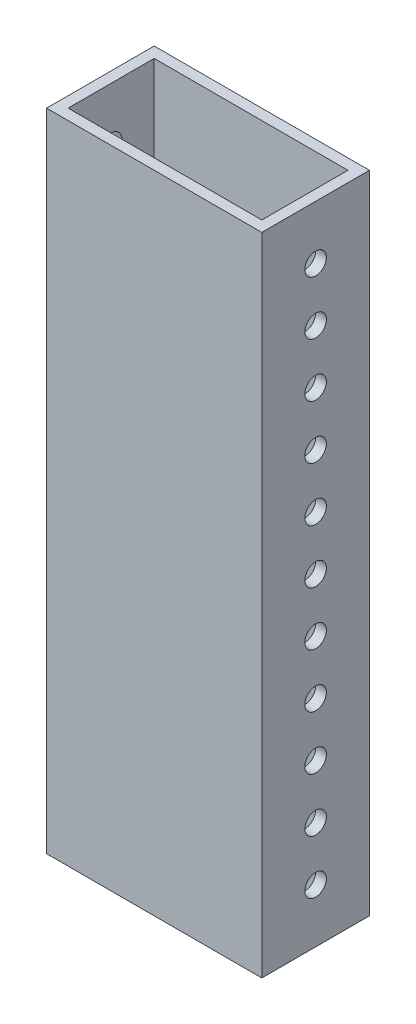
SolidWorks part; units mm, degrees
ref_plane "Front Plane" through (0, 0, 0) normal (0, 0, 1) x (1, 0, 0)
ref_plane "Top Plane" through (0, 0, 0) normal (0, 1, 0) x (1, 0, 0)
ref_plane "Right Plane" through (0, 0, 0) normal (1, 0, 0) x (0, 0, -1)
sketch "Sketch1" plane through (0, 0, 0) normal (0, 1, 0) x (1, 0, 0)
  line L1 (-59.9507, 17.7211) -> (-9.1507, 17.7211)
  line L2 (-59.9507, 17.7211) -> (-59.9507, -7.6789)
  line L3 (-59.9507, -7.6789) -> (-9.1507, -7.6789)
  line L4 (-9.1507, 17.7211) -> (-9.1507, -7.6789)
  line L5 (-59.9507, 17.7211) -> (-9.1507, -7.6789) construction
  line L6 (-59.9507, -7.6789) -> (-9.1507, 17.7211) construction
  line L7 (-57.4107, 15.1811) -> (-11.6907, 15.1811)
  line L8 (-57.4107, 15.1811) -> (-57.4107, -5.1389)
  line L9 (-57.4107, -5.1389) -> (-11.6907, -5.1389)
  line L10 (-11.6907, 15.1811) -> (-11.6907, -5.1389)
  line L11 (-57.4107, 15.1811) -> (-11.6907, -5.1389) construction
  line L12 (-57.4107, -5.1389) -> (-11.6907, 15.1811) construction
  point P0 (-34.5507, 5.0211)
  point P5 (-34.5507, 5.0211)
  dimension "D1" = 25.4
  dimension "D2" = 50.8
  dimension "D3" = 2.54
  dimension "D4" = 2.54
  dimension "D5" = 2.54
  dimension "D6" = 2.54
extrude "Boss-Extrude2" add sketch "Sketch1" along normal blind 152.4
sketch "Sketch2" plane through (-9.1507, 0, 0) normal (1, 0, 0) x (0, 0, -1)
  line L0 (-7.6789, 152.4) -> (17.7211, 152.4) construction
  line L1 (17.7211, 152.4) -> (17.7211, 0) construction
  circle A0 centre (5.0211, 139.7) radius 2.54
  circle A1 centre (5.0211, 127) radius 2.54
  circle A2 centre (5.0211, 114.3) radius 2.54
  circle A3 centre (5.0211, 101.6) radius 2.54
  circle A4 centre (5.0211, 88.9) radius 2.54
  circle A5 centre (5.0211, 76.2) radius 2.54
  circle A6 centre (5.0211, 63.5) radius 2.54
  circle A7 centre (5.0211, 50.8) radius 2.54
  circle A8 centre (5.0211, 38.1) radius 2.54
  circle A9 centre (5.0211, 25.4) radius 2.54
  circle A10 centre (5.0211, 12.7) radius 2.54
  dimension "D1" = 5.08
  dimension "D2" = 12.7
  dimension "D3" = 12.7
  dimension "D5" = 12.7
  dimension "D4" = 11
extrude "Cut-Extrude1" cut sketch "Sketch2" against normal blind 127
